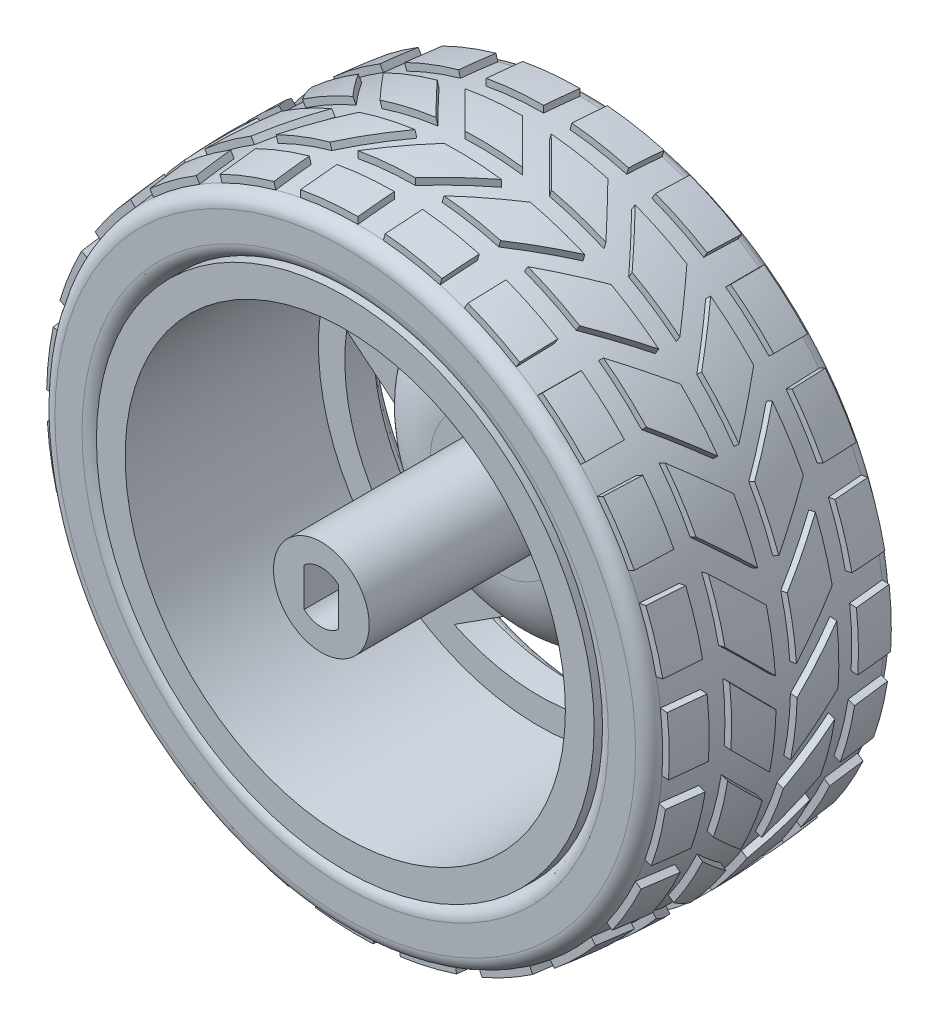
SolidWorks part; units mm, degrees
ref_plane "Front Plane" through (0, 0, 0) normal (0, 0, 1) x (1, 0, 0)
ref_plane "Top Plane" through (0, 0, 0) normal (0, 1, 0) x (1, 0, 0)
ref_plane "Right Plane" through (0, 0, 0) normal (1, 0, 0) x (0, 0, -1)
sketch "Sketch1" plane through (0, 0, 0) normal (1, 0, 0) x (0, 0, -1)
  line L0 (0, 0) -> (31.68, 0) construction
  line L1 (0, 0) -> (0, 5)
  line L2 (0, 5) -> (18.4, 5)
  line L3 (18.4, 5) -> (18.4, 7)
  line L4 (2.5, 26) -> (29, 26)
  line L5 (29, 26) -> (29, 24.5)
  line L6 (28.2, 22.5) -> (25.7, 22.5)
  line L7 (24.5, 0) -> (24.5, 5)
  line L8 (24.5, 5) -> (22.4, 5)
  line L9 (22.4, 5) -> (22.4, 7)
  line L10 (27.5, 12.1) -> (27.5, 19)
  line L11 (0, 0) -> (24.5, 0)
  line L12 (29, 24.5) -> (28.2, 24.5)
  line L13 (28.2, 24.5) -> (28.2, 22.5)
  line L14 (27.5, 12.1) -> (35.6714, 12.1) construction
  line L15 (2.5, 23) -> (22.7, 23)
  line L16 (22.7, 23) -> (22.7, 14.7311)
  line L17 (2.5, 23) -> (2.5, 26)
  arc A0 (22.4, 7) -> (27.5, 12.1) centre (27.5, 7) cw
  arc A1 (27.5, 19) -> (25.7, 22.5) centre (23.1972, 19) ccw
  arc A2 (18.4, 7) -> (22.7, 14.7311) centre (27.5, 7) cw
  dimension "D1" = 52
  dimension "D14" = 3
  dimension "D16" = 4
  dimension "D2" = 10
  dimension "D3" = 10
  dimension "D4" = 3
  dimension "D5" = 1.5
  dimension "D6" = 0.8
  dimension "D7" = 1.5
  dimension "D8" = 3.5
  dimension "D9" = 29
  dimension "D10" = 2
  dimension "D11" = 5.1
  dimension "D12" = 2.5
  dimension "D13" = 3.5
  dimension "D15" = 26.5
  dimension "D17" = 3
revolve "Revolve1" add sketch "Sketch1" angle 360 about L0
sketch "Sketch2" plane through (0, 0, -27.5) normal (0, 0, -1) x (-1, 0, 0)
  line L0 (0, 0) -> (0, 22.5) construction
  line L1 (0, 22.5) -> (-21.3988, 6.9529)
  line L2 (-21.3988, 6.9529) -> (-13.2252, -18.2029)
  line L3 (-13.2252, -18.2029) -> (13.2252, -18.2029)
  line L4 (13.2252, -18.2029) -> (21.3988, 6.9529)
  line L5 (21.3988, 6.9529) -> (0, 22.5)
  line L6 (0, 0) -> (-21.3988, 6.9529) construction
  line L7 (-20.4361, 9.4136) -> (-10.9391, 9.9525)
  line L8 (-2.6377, 22.3449) -> (-6.085, 13.4792)
  line L9 (0, 0) -> (-17.1718, 23.6349) construction
  line L12 (-10.9391, 9.9525) -> (-6.085, 13.4792) construction
  circle A0 centre (0, 0) radius 18.2029 construction
  circle A2 centre (0, 0) radius 22.5 construction
  circle A3 centre (0, 0) radius 22.5 construction
  arc A4 (-10.9391, 9.9525) -> (-6.085, 13.4792) centre (-11.2533, 15.4888) ccw
  circle A5 centre (0, 0) radius 12.1 construction
  circle A6 centre (0, 0) radius 22.5
  circle M6 centre (0, 0) radius 19
  dimension "D1" = 22
  dimension "D3" = 1.5
  dimension "D2" = 36
  dimension "D4" = 6
extrude "Cut-Extrude1" cut sketch "Sketch2" against normal up to next contours L8 A6 L7 L1 M6 | L7 A4 L8 L1 M6 | L1 M6 | L8 L1 M6 | L1 L7 M6 region at (4.6443, 18.811, -27.5) region at (11.8659, 16.332, -27.5) region at (9.624, 13.2463, -27.5) region at (10.8871, 14.9849, -27.5) region at (16.4551, 10.2299, -27.5)
pattern_circular "CirPattern1" count 5 over 360 about axis through (0, 0, -29) along (0, 0, 1) of "Cut-Extrude1"
sketch "Sketch3" plane through (0, 0, -27.5) normal (0, 0, -1) x (-1, 0, 0)
  line L0 (0, 0) -> (0, 22.5) construction
  arc A0 (2.6377, 22.3449) -> (-2.6377, 22.3449) centre (0, 0) ccw construction
  circle A1 centre (0, 16.85) radius 0.75
  circle A2 centre (0, 0) radius 12.1 construction
  dimension "D1" = 4
  dimension "D2" = 1.5
extrude "Cut-Extrude2" cut sketch "Sketch3" against normal blind 1
pattern_circular "CirPattern2" count 5 over 360 about axis through (0, 0, -29) along (0, 0, 1) of "Cut-Extrude2"
sketch "Sketch4" plane through (0, 0, -22.4) normal (0, 0, -1) x (-1, 0, 0)
  line L0 (0, 0) -> (0, 10.5062) construction
  circle A0 centre (0, 0) radius 5 construction
  circle A1 centre (0, 0) radius 7 construction
  circle A2 centre (0, 0) radius 5 construction
  circle A3 centre (0, 0) radius 7 construction
  circle A4 centre (0, 0) radius 6 construction
  circle A5 centre (0, 6) radius 0.75
  dimension "D1" = 1
  dimension "D2" = 1.5
extrude "Boss-Extrude1" add sketch "Sketch4" along normal blind 1.5
pattern_circular "CirPattern3" count 4 over 360 about axis through (0, 0, -29) along (0, 0, 1) of "Boss-Extrude1"
fillet "Fillet1" radius 0.75 4 edges at (6, 0.75, -23.9) (0.75, -6, -23.9) (-6, -0.75, -23.9) (-0.75, 6, -23.9)
sketch "Sketch5" plane through (0, 0, 0) normal (0, 0, 1) x (1, 0, 0)
  line L0 (-1.8, 2.0125) -> (-1.8, -2.0125)
  line L2 (1.8, -2.0125) -> (1.8, 2.0125)
  circle A0 centre (0, 0) radius 2.7
  dimension "D1" = 5.4
  dimension "D2" = 3.6
extrude "Cut-Extrude3" cut sketch "Sketch5" against normal offset from surface (21.5 mm away) 3 contours L2 A0 L0 region at (0, 0, 0) up to face at (5, 0, -24.5)
sketch "Sketch6" plane through (0, 0, -22.7) normal (0, 0, 1) x (1, 0, 0)
  circle A0 centre (0, 0) radius 20.25
  circle A1 centre (0, 0) radius 23 construction
  circle A2 centre (0, 0) radius 23
  dimension "D1" = 40.5
extrude "Boss-Extrude2" add sketch "Sketch6" against normal blind 3
fillet "Fillet2" radius 0.5 2 edges at (24.5, 0, -29) (22.5, 0, -28.2)
sketch "Sketch7" plane through (0, 0, 0) normal (1, 0, 0) x (0, 0, -1)
  line L0 (29, 26) -> (2.5, 26) construction
  line L1 (29, 26) -> (2.5, 26)
  line L2 (4, 26) -> (4, 19.2647) construction
  line L3 (27.5, 26) -> (27.5, 19.2647) construction
  line L4 (2.5, 26) -> (2.5, -26) construction
  line L5 (29, -26) -> (29, 26) construction
  line L6 (2.5, 26) -> (2.5, 42.0757) construction
  line L7 (28.35, 26) -> (28.35, 42.0757) construction
  line L8 (2.5, 30.3323) -> (2.5, 27.5)
  line L9 (28.35, 30.3323) -> (28.35, 27.5)
  line L10 (0, 0) -> (37.9684, 0) construction
  line L11 (0, 5) -> (0, -5) construction
  line L12 (15.425, 32.5) -> (47.3444, 32.5) construction
  line L13 (2.5, 30.3323) -> (28.35, 30.3323) construction
  line L14 (28.35, 27.5) -> (2.5, 27.5) construction
  arc A0 (4, 26) -> (2.5, 27.5) centre (4, 27.5) cw
  arc A1 (2.5, 31.6576) -> (28.35, 31.6576) centre (15.425, -67.0756) cw
  arc A2 (27.5, 26) -> (28.35, 27.5) centre (26.6015, 27.5) ccw
  arc A3 (3.8253, 31.8221) -> (2.5, 30.3323) centre (4, 30.3323) ccw
  arc A4 (27.0247, 31.8221) -> (28.35, 30.3323) centre (26.85, 30.3323) cw
  dimension "D4" = 32.5
  dimension "D1" = 1.5
  dimension "D2" = 1.5
  dimension "D3" = 0.65
revolve "Revolve2" add sketch "Sketch7" angle 360 about L10 region at (0, 29.1194, -15.4335)
ref_plane "Plane1" through (0, 35, 0) normal (0, 1, 0) x (1, 0, 0)
sketch "Sketch8" plane through (0, 35, 0) normal (0, 1, 0) x (1, 0, 0)
  line L0 (0, 0) -> (0, 38.366) construction
  line L1 (-5, 0) -> (5, 0) construction
  line L2 (26.5551, 27.0247) -> (26.5551, 3.8253) construction
  line L3 (31.8221, 27.0247) -> (-31.8221, 27.0247) construction
  line L4 (31.8221, 3.8253) -> (-31.8221, 3.8253) construction
  line L5 (26.5551, 15.425) -> (0, 15.425) construction
  line L6 (-6, 27.0247) -> (0, 27.0247)
  line L7 (0, 27.0247) -> (0, 23.225)
  line L8 (0, 23.225) -> (-6, 23.225)
  line L9 (-6, 23.225) -> (-6, 27.0247)
  line L10 (0, 3.8253) -> (0, 7.625)
  line L11 (0, 7.625) -> (-6, 7.625)
  line L12 (-6, 7.625) -> (-6, 3.8253)
  line L13 (-6, 3.8253) -> (0, 3.8253)
  line L14 (-6, 21.025) -> (0, 21.025)
  line L15 (0, 21.025) -> (4.5, 16.525)
  line L16 (4.5, 16.525) -> (-1.5, 16.525)
  line L17 (-1.5, 16.525) -> (-6, 21.025)
  line L18 (-1.5, 14.325) -> (4.5, 14.325)
  line L19 (4.5, 14.325) -> (0, 9.825)
  line L20 (0, 9.825) -> (-6, 9.825)
  line L21 (-6, 9.825) -> (-1.5, 14.325)
  line L22 (-6, 23.225) -> (-6, 21.025) construction
  line L23 (-6, 9.825) -> (-6, 7.625) construction
  line L24 (-6, 21.025) -> (-6, 9.825) construction
  line L25 (-1.5, 16.525) -> (-1.5, 14.325) construction
  line L26 (4.5, 16.525) -> (4.5, 14.325) construction
  dimension "D1" = 2.2
  dimension "D2" = 2.2
  dimension "D3" = 2.2
  dimension "D4" = 6
  dimension "D5" = 4.5
extrude "Boss-Extrude3" add sketch "Sketch8" against normal up to surface (3.37 mm away) up to face at (31.8221, 0, -27.0247)
pattern_circular "CirPattern4" count 23 over 360 about axis through (0, 0, -2.5) along (0, 0, 1) of "Boss-Extrude3"
sketch "Sketch9" plane through (0, 0, 0) normal (1, 0, 0) x (0, 0, -1)
  line L0 (28.35, 30.3323) -> (28.35, 27.5) construction
  line L1 (2.5, 30.3323) -> (2.5, 27.5) construction
  line L2 (29, 26) -> (2.5, 26) construction
  line L3 (28.35, 30.3323) -> (28.35, 27.5) construction
  line L4 (2.5, 30.3323) -> (2.5, 27.5) construction
  line L5 (29, 26) -> (2.5, 26) construction
  line L6 (2.4091, 32.3517) -> (2.4091, 40.815)
  line L7 (2.4091, 40.815) -> (28.4409, 40.815)
  line L8 (28.4409, 40.815) -> (28.4409, 32.3517)
  line L9 (0, 0) -> (55.1944, 0) construction
  arc A1 (27.5, 26) -> (28.35, 27.5) centre (26.6015, 27.5) ccw construction
  arc A2 (28.35, 30.3323) -> (27.0247, 31.8221) centre (26.85, 30.3323) ccw construction
  arc A3 (28.35, 31.6576) -> (2.5, 31.6576) centre (15.425, -67.0756) ccw construction
  arc A4 (2.5, 27.5) -> (4, 26) centre (4, 27.5) ccw construction
  arc A5 (3.8253, 31.8221) -> (2.5, 30.3323) centre (4, 30.3323) ccw construction
  arc A6 (27.5, 26) -> (28.35, 27.5) centre (26.6015, 27.5) ccw construction
  arc A7 (28.35, 30.3323) -> (27.0247, 31.8221) centre (26.85, 30.3323) ccw construction
  arc A8 (28.35, 31.6576) -> (2.5, 31.6576) centre (15.425, -67.0756) ccw construction
  arc A9 (2.5, 27.5) -> (4, 26) centre (4, 27.5) ccw construction
  arc A10 (3.8253, 31.8221) -> (2.5, 30.3323) centre (4, 30.3323) ccw construction
  arc A11 (28.4409, 32.3517) -> (2.4091, 32.3517) centre (15.425, -67.0756) ccw
  dimension "D1" = 0.7
revolve "Cut-Revolve1" cut sketch "Sketch9" angle 360 about L9
